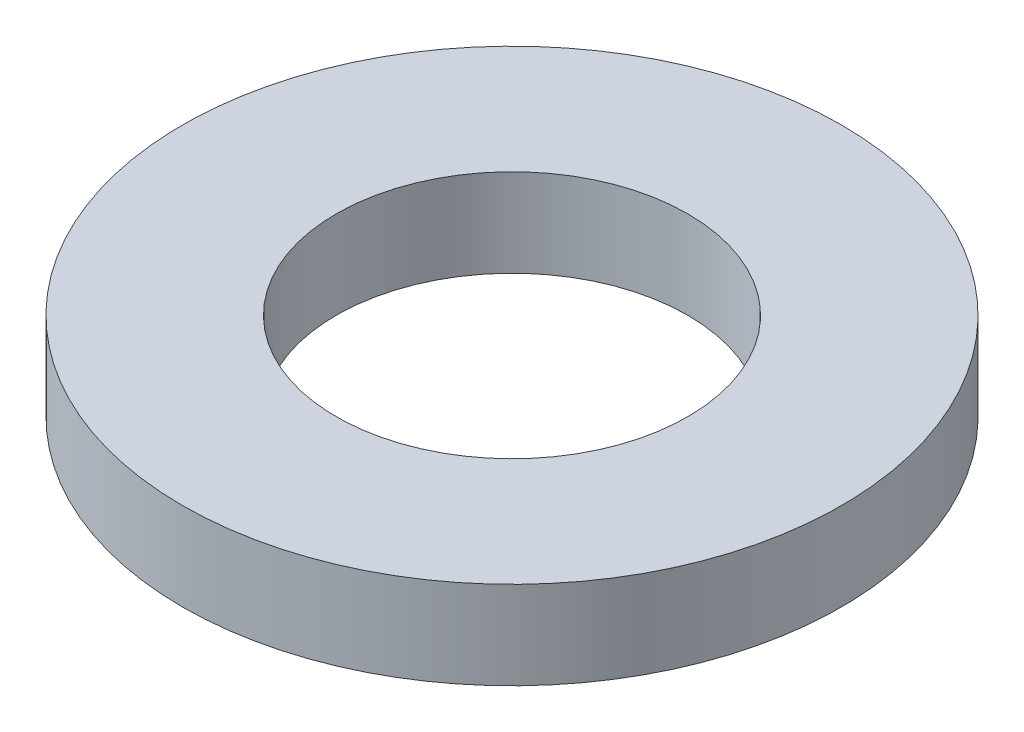
SolidWorks part; units mm, degrees
ref_plane "Face" through (0, 0, 0) normal (0, 0, 1) x (1, 0, 0)
ref_plane "Dessus" through (0, 0, 0) normal (0, 1, 0) x (1, 0, 0)
ref_plane "Droite" through (0, 0, 0) normal (1, 0, 0) x (0, 0, -1)
ref_axis "Axe1" through (0, 6.1904, 0) along (0, -1, 0)
sketch "Esquisse1" plane through (0, 0, 0) normal (0, 0, 1) x (1, 0, 0)
  line L1 (0, 0) -> (0, 2.5443) construction
  line L2 (1.6, 0) -> (1.6, 0.8)
  line L3 (1.6, 0) -> (3, 0)
  line L4 (3, 0) -> (3, 0.8)
  line L5 (3, 0.8) -> (1.6, 0.8)
  line L6 (1.6, 0) -> (-1.6, 0) construction
  line L7 (3, 0) -> (-3, 0) construction
  dimension "Epaisseur" = 0.8
  dimension "Diamètre de passage" = 3.2
  dimension "Diamètre extérieur" = 6
revolve "Base-Révolution" add sketch "Esquisse1" angle 360 about L1
